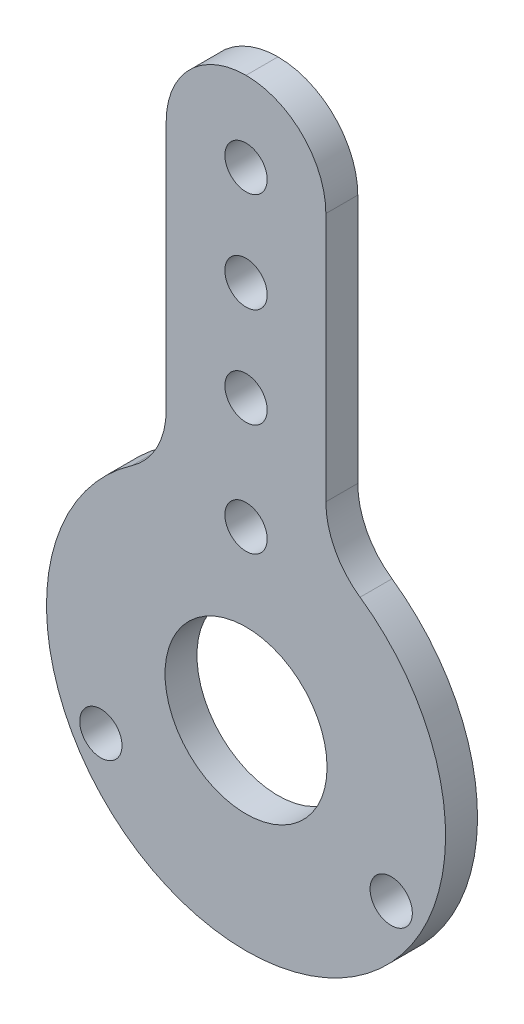
SolidWorks part; units mm, degrees
material "Thornel Mat VMA"
ref_plane "前视基准面" through (0, 0, 0) normal (0, 0, 1) x (1, 0, 0)
ref_plane "上视基准面" through (0, 0, 0) normal (0, 1, 0) x (1, 0, 0)
ref_plane "右视基准面" through (0, 0, 0) normal (1, 0, 0) x (0, 0, -1)
sketch "草图1" plane through (0, 0, 0) normal (0, 0, 1) x (1, 0, 0)
  line L0 (-10, 70) -> (-10, 22.9129)
  line L1 (-10, 70) -> (10, 70)
  line L2 (10, 70) -> (10, 22.9129)
  line L3 (0, 0) -> (0, 70) construction
  circle A0 centre (0, 0) radius 10.15
  arc A1 (-10, 22.9129) -> (10, 22.9129) centre (0, 0) ccw
  circle A2 centre (0, 0) radius 21 construction
  circle A3 centre (0, 21) radius 2.65
  circle A4 centre (18.1865, -10.5) radius 2.65
  circle A5 centre (-18.1865, -10.5) radius 2.65
  circle A6 centre (0, 60) radius 2.65
  circle A7 centre (0, 35) radius 2.65
  circle A8 centre (0, 47.5) radius 2.65
  point P13 (0, 0)
  dimension "D1" = 20.3
  dimension "D2" = 50
  dimension "D3" = 42
  dimension "D5" = 5.3
  dimension "D8" = 5.3
  dimension "D9" = 10
  dimension "D10" = 12.5
  dimension "D11" = 12.5
  dimension "D6" = 70
  dimension "D7" = 20
  dimension "D4" = 3
extrude "凸台-拉伸1" add sketch "草图1" along normal blind 4
fillet "圆角1" radius 10 4 edges at (10, 22.9129, 2) (10, 70, 2) (-10, 70, 2) (-10, 22.9129, 2)
